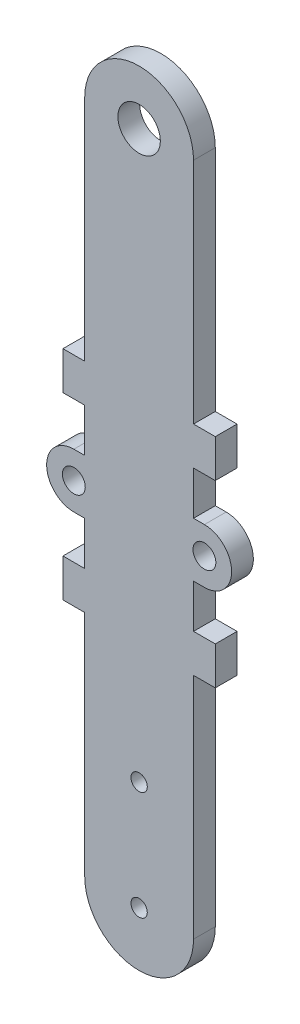
SolidWorks part; units mm, degrees
ref_plane "Plan de face" through (0, 0, 0) normal (0, 0, 1) x (1, 0, 0)
ref_plane "Plan de dessus" through (0, 0, 0) normal (0, 1, 0) x (1, 0, 0)
ref_plane "Plan de droite" through (0, 0, 0) normal (1, 0, 0) x (0, 0, -1)
sketch "Esquisse1" plane through (0, 0, 0) normal (0, 0, 1) x (1, 0, 0)
  line L0 (-10, -72) -> (10, 72) construction
  line L1 (10, -72) -> (-10, -72)
  line L2 (10, -72) -> (10, 72)
  line L3 (10, 72) -> (-10, 72)
  line L4 (-10, -72) -> (-10, 72)
  circle A0 centre (0, -62) radius 1.5
  circle A1 centre (0, 62) radius 3.9
  point P8 (0, -72)
  point P10 (0, 0)
  dimension "D3" = 3
  dimension "D2" = 10
  dimension "D5" = 7.8
  dimension "D1" = 20
  dimension "D4" = 10
  dimension "D6" = 124
  dimension "D7" = 10
extrude "Boss.-Extru.1" add sketch "Esquisse1" along normal blind 4
fillet "Congé1" 2 edges at (-10, 72, 2) (10, 72, 2) type full round first side face at (-10, 0, 2) second side face at (10, 0, 2) middle face at (0, 72, 2)
sketch "Esquisse2" plane through (0, 0, 4) normal (0, 0, 1) x (1, 0, 0)
  line L7 (-14, 0) -> (-10, 0) construction
  line L8 (-10, 62) -> (-10, -72) construction
  line L9 (-10, 5) -> (-10, -5)
  line L10 (-10, -5) -> (-12, -5)
  line L11 (-10, 5) -> (-12, 5)
  line L12 (-10, 20) -> (-14, 20) construction
  line L13 (-14, 20) -> (-14, -20) construction
  line L14 (-10, 20) -> (-14, 20)
  line L15 (-10, 20) -> (-10, 13)
  line L16 (-10, 13) -> (-14, 13)
  line L17 (-14, 20) -> (-14, 13)
  line L18 (-10, -20) -> (-14, -20) construction
  line L20 (-10, -20) -> (-14, -20)
  line L21 (-10, -20) -> (-10, -13)
  line L22 (-10, -13) -> (-14, -13)
  line L23 (-14, -20) -> (-14, -13)
  arc A0 (-12, -5) -> (-17, 0) centre (-12, 0) cw
  circle A1 centre (-12, 0) radius 2.1
  arc A2 (-12, 5) -> (-17, 0) centre (-12, 0) ccw
  line M10 (-10, 62) -> (-10, -72)
  dimension "D1" = 4.2
  dimension "D2" = 5
  dimension "D3" = 7
  dimension "D4" = 7
extrude "Boss.-Extru.2" add sketch "Esquisse2" against normal blind 4 contours A1 L11 A2 A0 L10 L9 M10 | L23 L20 L22 M10 | L14 L17 L16 M10 region at (-12, -16.5, 4) region at (-10.1221, 2.8202, 4) region at (-12, 16.5, 4)
sketch "Esquisse3" plane through (0, 0, 0) normal (0, 0, -1) x (-1, 0, 0)
  circle A0 centre (0, -42) radius 1.5
  circle A2 centre (0, -62) radius 1.5 construction
  dimension "D1" = 3
  dimension "D2" = 20
extrude "Enlèv. mat.-Extru.1" cut sketch "Esquisse3" against normal through all
fillet "Congé2" 2 edges at (-10, -72, 2) (10, -72, 2) type full round first side face at (-10, -46, 2) second side face at (10, -5, 2) middle face at (0, -72, 2)
sketch "Esquisse4" plane through (0, 0, 4) normal (0, 0, 1) x (1, 0, 0)
  circle A0 centre (-12, 0) radius 2.1
extrude "Enlèv. mat.-Extru.2" cut sketch "Esquisse4" against normal through all
mirror "Symétrie1" about plane through (0, 0, 0) normal (1, 0, 0) of "Enlèv. mat.-Extru.2", "Boss.-Extru.2"
